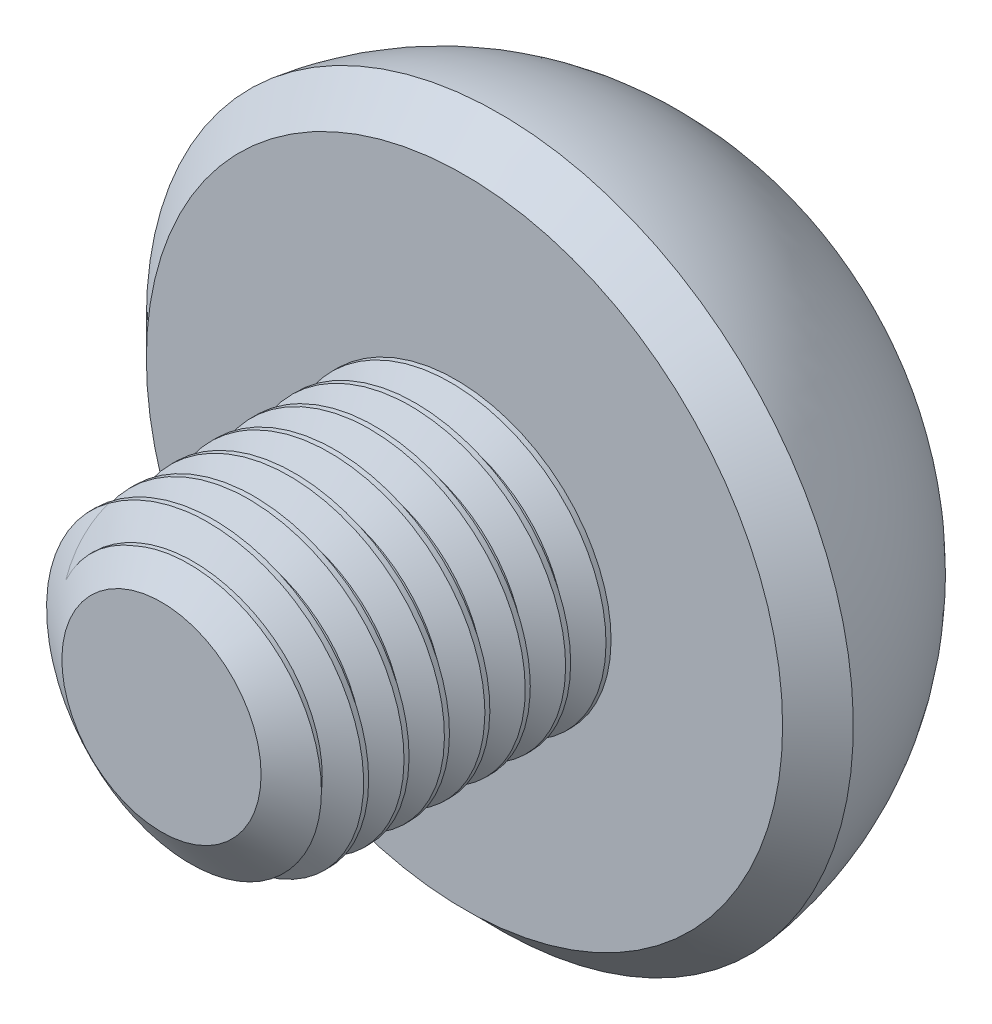
SolidWorks part; units mm, degrees
other "DetailItem1"
ref_plane "Front Plane" through (0, 0, 0) normal (0, 0, 1) x (1, 0, 0)
ref_plane "Top Plane" through (0, 0, 0) normal (0, 1, 0) x (1, 0, 0)
ref_plane "Right Plane" through (0, 0, 0) normal (1, 0, 0) x (0, 0, -1)
sketch "Sketch1" plane through (0, 0, 0) normal (0, 0, 1) x (1, 0, 0)
  circle A0 centre (0, 0) radius 1.5
  dimension "OD" = 3
extrude "Extrude1" add sketch "Sketch1" against normal blind 3
sketch "Sketch2" plane through (0, 0, 0) normal (0, 0, 1) x (1, 0, 0)
  circle A0 centre (0, 0) radius 1.5 construction
  circle A1 centre (0, 0) radius 1.5
curve "Helix/Spiral1" pitch 0.4 height 3.4 radius 1.5 centre (0, 0, 0) axis (0, 0, -1) start towards (0, 1, 0) parameters "pitch"=0.4
sketch "Sketch3" plane through (0, 0, 0) normal (1, 0, 0) x (0, 0, -1)
  line L0 (-0.35, 1.5) -> (-0.2, 1.2402)
  line L1 (-0.2, 1.2402) -> (-0.15, 1.2402)
  line L2 (-0.15, 1.2402) -> (0, 1.5)
  line L3 (-0.35, 1.5) -> (0, 1.5)
  line L4 (-0.175, 1.5) -> (-0.175, 1.2402) construction
  line L5 (-0.275, 1.3701) -> (-0.075, 1.3701) construction
  line L6 (0, 1.5) -> (0, -1.5) construction
  dimension "D1" = 0.05
  dimension "D2" = 0.2
  dimension "D3" = 60
sweep "Cut-Sweep1" cut profiles "Sketch3" path "Helix/Spiral1" align with end faces yes
sketch "Sketch4" plane through (0, 0, 0) normal (1, 0, 0) x (0, 0, -1)
  line L0 (0.3598, 1.5) -> (0, 0.9862)
  line L1 (0, 0.9862) -> (0, 1.5)
  line L2 (0.3598, 1.5) -> (0, 1.5)
  line L3 (-0.35, 1.5) -> (0, 1.5) construction
  line L4 (0, 0) -> (7.0209, 0) construction
  dimension "D1" = 55
  dimension "D2" = 0.254
revolve "Cut-Revolve1" cut sketch "Sketch4" angle 360 about L4
sketch "Sketch6" plane through (0, 0, -3) normal (0, 0, -1) x (-1, 0, 0)
  circle A0 centre (0, 0) radius 3.5
  dimension "head dia" = 7
extrude "Extrude2" add sketch "Sketch6" along normal blind 3
sketch "Sketch7" plane through (0, 0, -6) normal (0, 0, -1) x (-1, 0, 0)
  line L1 (0, 0.866) -> (-0.75, 0.433)
  line L2 (-0.75, 0.433) -> (-0.75, -0.433)
  line L3 (-0.75, -0.433) -> (0, -0.866)
  line L4 (0, -0.866) -> (0.75, -0.433)
  line L5 (0.75, -0.433) -> (0.75, 0.433)
  line L6 (0.75, 0.433) -> (0, 0.866)
  circle A0 centre (0, 0) radius 0.75 construction
  dimension "hex dia" = 1.5
sketch "Sketch8" plane through (0, 0, -6) normal (0, 0, -1) x (-1, 0, 0)
  circle A0 centre (0, 0) radius 0.866
chamfer "Chamfer1" distance 0.35 angle 45 1 edges at (-3.5, 0, -3)
sketch "Sketch10" plane through (0, 0, -3) normal (0, 0, 1) x (1, 0, 0)
  circle A1 centre (0, 0) radius 1.5
  circle A2 centre (0, 0) radius 1.5
  dimension "D1" = 0
ref_plane "Plane1" through (0, 0, 0) normal (0, 0, 1) x (1, 0, 0)
extrude "partial thread" [suppressed] add sketch "Sketch10" along normal up to surface (2 mm away) separate body up to plane "Plane1"
chamfer "Chamfer2" [suppressed] distance 0.06 angle 45
combine bodies "Combine1" [suppressed] operation type add bodies to combine 107 108
sketch "Sketch9" plane through (0, 0, 0) normal (1, 0, 0) x (0, 0, -1)
  line L0 (0, 1.5) -> (0, -1.5) construction
  line L1 (1, 1.5) -> (1, -1.5) construction
  dimension "D1" = 1
fillet "Redondeo1" radius 3 1 edges at (-3.5, 0, -6)
ref_plane "Plano1" through (0, 0, -6) normal (0, 0, -1) x (-1, 0, 0)
sketch "Croquis1" plane through (0, 0, -6) normal (0, 0, -1) x (-1, 0, 0)
  line L1 (0.3, -2.5) -> (-0.3, -2.5)
  line L2 (0.3, -2.5) -> (0.3, 2.5)
  line L3 (0.3, 2.5) -> (-0.3, 2.5)
  line L4 (-0.3, -2.5) -> (-0.3, 2.5)
  line L5 (0.3, -2.5) -> (-0.3, 2.5) construction
  line L6 (0.3, 2.5) -> (-0.3, -2.5) construction
  line L7 (2.5, -0.3) -> (-2.5, -0.3)
  line L8 (2.5, -0.3) -> (2.5, 0.3)
  line L9 (2.5, 0.3) -> (-2.5, 0.3)
  line L10 (-2.5, -0.3) -> (-2.5, 0.3)
  line L11 (2.5, -0.3) -> (-2.5, 0.3) construction
  line L12 (2.5, 0.3) -> (-2.5, -0.3) construction
  point P0 (0, 0)
  point P6 (0, 0)
  dimension "D1" = 5
  dimension "D2" = 0.6
extrude "Cortar-Extruir1" cut sketch "Croquis1" against normal blind 1 contours L2 L7 L4 L1 | L10 L7 L4 L9 | L9 L2 L3 L4 | L2 L9 L4 L7 | L8 L9 L2 L7 | L7 L10 L9 L8 region at (0, -1.4, -6) region at (0, 0, -6) region at (-1.4, 0, -6) region at (1.4, 0, -6) region at (0, 1.4, -6)
equation "\"D3@Helix/Spiral1\" = \"screw length@Extrude1\"+\"pitch@Helix/Spiral1\""
equation "\"D1@Sketch3\" = \"pitch@Helix/Spiral1\"*.125"
equation "\"D2@Sketch3\" = \"pitch@Helix/Spiral1\"*.5"
equation "\"D1@Chamfer1\" = \"head dia@Sketch6\"*.05"
equation "\"D1@Sketch9\" = \"pitch@Helix/Spiral1\"*2.5"
equation "\"D1@Chamfer2\"=\"OD@Sketch1\"*.02"
